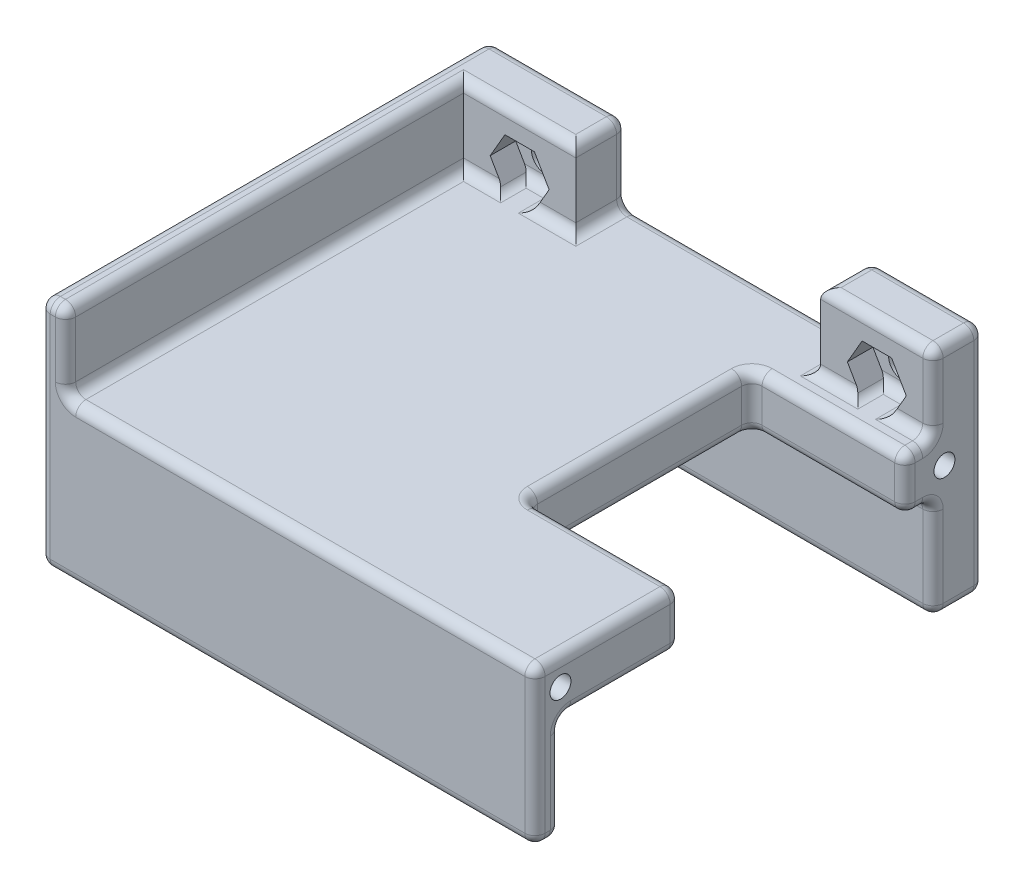
SolidWorks part; units mm, degrees
material "ABS"
ref_plane "Front Plane" through (0, 0, 0) normal (0, 0, 1) x (1, 0, 0)
ref_plane "Top Plane" through (0, 0, 0) normal (0, 1, 0) x (1, 0, 0)
ref_plane "Right Plane" through (0, 0, 0) normal (1, 0, 0) x (0, 0, -1)
sketch "Sketch16" plane through (0, 0, 0) normal (0, 0, 1) x (1, 0, 0)
  line L0 (-17.5, 0) -> (17.5, 0) construction
  line L2 (-16.0566, 2.5) -> (-18.9434, 2.5)
  line L3 (-18.9434, 2.5) -> (-20.3868, 0)
  line L4 (-20.3868, 0) -> (-18.9434, -2.5)
  line L5 (-18.9434, -2.5) -> (-16.0566, -2.5)
  line L6 (-16.0566, -2.5) -> (-14.6132, 0)
  line L7 (-14.6132, 0) -> (-16.0566, 2.5)
  line L8 (18.9434, 2.5) -> (16.0566, 2.5)
  line L9 (16.0566, 2.5) -> (14.6132, 0)
  line L10 (14.6132, 0) -> (16.0566, -2.5)
  line L11 (16.0566, -2.5) -> (18.9434, -2.5)
  line L12 (18.9434, -2.5) -> (20.3868, 0)
  line L13 (20.3868, 0) -> (18.9434, 2.5)
  line L14 (-23, 5) -> (-12, 5)
  line L15 (-23, 5) -> (-23, -2.5)
  line L16 (-23, -2.5) -> (-12, -2.5)
  line L17 (-12, 5) -> (-12, -2.5)
  line L18 (12, 5) -> (23, 5)
  line L19 (12, 5) -> (12, -2.5)
  line L20 (12, -2.5) -> (23, -2.5)
  line L21 (23, 5) -> (23, -2.5)
  line L22 (-23, 5) -> (-25.5, 5)
  line L23 (-23, 5) -> (-23, -17.8)
  line L24 (-23, -17.8) -> (-25.5, -17.8)
  line L25 (-25.5, 5) -> (-25.5, -17.8)
  line L26 (-23, -2.5) -> (23, -2.5)
  line L27 (-23, -2.5) -> (-23, -7.8)
  line L28 (-23, -7.8) -> (23, -7.8)
  line L29 (23, -2.5) -> (23, -7.8)
  line L30 (-23, -17.8) -> (23, -17.8)
  line L31 (-23, -17.8) -> (-23, -7.8)
  line L32 (-23, -7.8) -> (23, -7.8)
  line L33 (23, -17.8) -> (23, -7.8)
  line L34 (23, 5) -> (25.5, 5) construction
  line L35 (23, 5) -> (23, -17.8) construction
  line L36 (23, -17.8) -> (25.5, -17.8) construction
  line L37 (25.5, 5) -> (25.5, -17.8) construction
  line L38 (25.5, 5) -> (28.5, 5) construction
  line L39 (25.5, 5) -> (25.5, -17.8) construction
  line L40 (25.5, -17.8) -> (28.5, -17.8) construction
  line L41 (28.5, 5) -> (28.5, -17.8) construction
  circle A0 centre (-17.5, 0) radius 2.5 construction
  circle A1 centre (17.5, 0) radius 2.5 construction
  point P4 (0, 0)
  point P28 (17.5, 5)
  point P30 (-17.5, 5)
  dimension "D1" = 35
  dimension "D2" = 5
  dimension "D3" = 46
  dimension "D4" = 2.5
  dimension "D5" = 7.8
  dimension "D6" = 2.5
  dimension "D7" = 2.5
  dimension "D8" = 10
  dimension "D9" = 3
extrude "Boss-Extrude1" add sketch "Sketch16" along normal blind 5 contours L17 L14 L15 L16 L4 L3 L2 L7 L6 | L21 L18 L19 L20 L10 L9 L8 L13 L12 | L23 L22 L25 L24 | L27 L26 L29 L28 | L31 L30 L33 L32 | L2 L3 L4 L5 L6 L7 | L19 L18 L21 L20 region at (-17.5, 2.6331, 0) region at (12.1331, 1.25, 0)
extrude "Cut-Extrude4" cut sketch "Sketch16<5>" against normal blind 2.5 from surface contours L6 L7 L2 L3 L4 L5 | L12 L13 L8 L9 L10 L11 region at (-17.5, 0, 0) region at (17.5, 0, 0) starting at face at (-0.625, -2.575, 5)
sketch "Sketch16<5>" plane through (0, 0, 0) normal (0, 0, 1) x (1, 0, 0) same geometry as "Sketch16"
extrude "Boss-Extrude2" add sketch "Sketch16<4>" along normal blind 41.5 contours L22 L25 L24 L23 L15 | L29 L20 L11 L26 L16 L5 L23 L28 region at (0, -5.15, 0) region at (-24.25, -6.4, 0)
sketch "Sketch16<4>" plane through (0, 0, 0) normal (0, 0, 1) x (1, 0, 0) same geometry as "Sketch16"
extrude "Boss-Extrude3" add sketch "Sketch16<6>" along normal blind 2.5 from surface contours L29 L20 L11 L26 L16 L5 L23 L28 | L22 L25 L24 L23 L15 | L30 L33 L28 L23 region at (0, -5.15, 0) region at (-24.25, -6.4, 0) region at (0, -12.8, 0) starting at face at (-12.125, -5.775, 41.5)
sketch "Sketch16<6>" plane through (0, 0, 0) normal (0, 0, 1) x (1, 0, 0) same geometry as "Sketch16"
sketch "Sketch17" plane through (0, -2.5, 0) normal (0, 1, 0) x (1, 0, 0)
  line L0 (23, -44) -> (23, -5) construction
  line L1 (23, -7.75) -> (8, -7.75)
  line L2 (23, -7.75) -> (23, -29.75)
  line L3 (23, -29.75) -> (8, -29.75)
  line L4 (8, -7.75) -> (8, -29.75)
  line L5 (23, -5) -> (18.9434, -5) construction
  dimension "D1" = 15
  dimension "D2" = 22
  dimension "D3" = 2.75
extrude "Cut-Extrude5" cut sketch "Sketch17" against normal through all
sketch "Sketch18" plane through (23, 0, 0) normal (1, 0, 0) x (0, 0, -1)
  line L0 (-41.5, -5.15) -> (-3.875, -5.15) construction
  line L1 (-29.75, -7.8) -> (-29.75, -2.5) construction
  line L2 (-44, -17.8) -> (-44, -2.5) construction
  line L3 (0, 5) -> (0, -17.8) construction
  line L4 (-7.75, -7.8) -> (-7.75, -2.5) construction
  point P0 (-41.5, -5.15)
  point P1 (-3.875, -5.15)
  point P4 (-29.75, -5.15)
  point P13 (-3.875, -5.15)
  point P15 (-41.5, -5.15)
  dimension "D1" = 2.5
  dimension "D2" = 3.875
  dimension "D3" = 7.75
hole_wizard "M2.5x0.45 Tapped Hole2" positions "Sketch18" profile "Sketch19" tap size "M2.5x0.45" standard "ANSI Metric"
sketch "Sketch19" plane through (23, -5.15, 41.5) normal (0, 1, 0) x (0, 0, -1)
  line L0 (0, 0) -> (0, 15.6159)
  line L1 (0, 15.6159) -> (1.025, 15)
  line L2 (1.025, 15) -> (1.025, 0)
  line L5 (1.025, 0) -> (0, 0)
  line L10 (0, 15.6159) -> (-1.025, 15) construction
  line L11 (0, -6.35) -> (0, 107.95) construction
  dimension "Tap Drill Dia." = 2.05
  dimension "Tap Drill Depth" = 15
  dimension "Drill Angle" = 118
cosmetic thread "Hole Thread3" parameters "D1"=5, "D2"=2.5
cosmetic thread "Hole Thread4" parameters "D1"=5, "D2"=2.5
fillet "Fillet1" radius 1 62 edges at (-23, 1.25, 44) (-12, 1.25, 0) (12, 1.25, 0) (23, 1.25, 5) (23, -2.5, 36.875) (0, -2.5, 44) (-23, -2.5, 24.5) (-20.9717, -2.5, 5) (-18.9434, -2.5, 3.75) (-17.5, -2.5, 2.5) (-16.0566, -2.5, 3.75) (-14.0283, -2.5, 5) (-12, -2.5, 2.5) (0, -2.5, 0) (12, -2.5, 2.5) (14.0283, -2.5, 5) (16.0566, -2.5, 3.75) (17.5, -2.5, 2.5) (18.9434, -2.5, 3.75) (20.9717, -2.5, 5) (23, -2.5, 6.375) (15.5, -2.5, 7.75) (8, -2.5, 18.75) (15.5, -2.5, 29.75) (23, -12.8, 5) (23, -12.8, 41.5) (0, -17.8, 41.5) (0, -17.8, 5) (15.5, -7.8, 7.75) (23, -7.8, 6.375) (0, -7.8, 5) (0, -7.8, 41.5) (23, -7.8, 35.625) (15.5, -7.8, 29.75) (-23, -12.8, 41.5) (-23, -7.8, 23.25) (-23, -12.8, 5) (-23, -17.8, 23.25) (8, -7.8, 18.75) (8, -5.15, 29.75) (8, -5.15, 7.75) (23, 5, 2.5) (17.5, 5, 5) (12, 5, 2.5) (17.5, 5, 0) (-17.5, 5, 5) (-23, 5, 24.5) (-24.25, 5, 44) (-25.5, 5, 22) (-18.75, 5, 0) (-12, 5, 2.5) (23, -17.8, 42.75) (23, -10.15, 44) (23, -5.15, 29.75) (-1.25, -17.8, 44) (-25.5, -6.4, 44) (-25.5, -6.4, 0) (23, -6.4, 0) (23, -17.8, 2.5) (-1.25, -17.8, 0) (-25.5, -17.8, 22) (23, -5.15, 7.75)
hole_wizard "M2.5 Clearance Hole1" positions "Sketch20" profile "Sketch21" hole size "M2.5" standard "ANSI Metric" end condition through all
sketch "Sketch20" plane through (0, 0, 0) normal (0, 0, -1) x (-1, 0, 0)
  point P0 (-17.5, 0)
  point P3 (17.5, 0)
sketch "Sketch21" plane through (17.5, 0, 0) normal (1, 0, 0) x (0, 1, 0)
  line L0 (0, 0) -> (0, 44)
  line L1 (0, 44) -> (1.35, 44)
  line L2 (1.35, 44) -> (1.35, 0)
  line L5 (1.35, 0) -> (0, 0)
  line L11 (0, -6.35) -> (0, 107.95) construction
  dimension "Thru Hole Dia." = 2.7
  dimension "Thru Hole Depth" = 44
equation "\"D2@Sketch18\"=\"D3@Sketch18\"/2"
